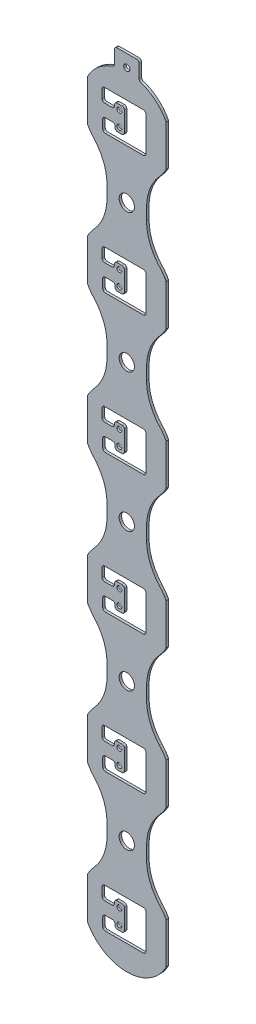
SolidWorks part; units mm, degrees
ref_plane "Plan de face" through (0, 0, 0) normal (0, 0, 1) x (1, 0, 0)
ref_plane "Plan de dessus" through (0, 0, 0) normal (0, 1, 0) x (1, 0, 0)
ref_plane "Plan de droite" through (0, 0, 0) normal (1, 0, 0) x (0, 0, -1)
sketch "Esquisse1" plane through (0, 0, 0) normal (0, 0, 1) x (1, 0, 0)
  line L1 (4, -28) -> (-4, -28)
  line L2 (4, -28) -> (4, -8.0623)
  line L4 (-4, -28) -> (-4, -8.0623)
  arc A0 (4, -8.0623) -> (-4, -8.0623) centre (0, 0) ccw
  point P4 (0, -28)
  dimension "D1" = 18
  dimension "D2" = 28
  dimension "D3" = 8
extrude "Boss.-Extru.1" add sketch "Esquisse1" along normal blind 0.508 contours A0 L4 L1 L2
pattern_linear "Répétition linéaire1" count 6 spacing 28 along (0, -1, 0) of "Boss.-Extru.1"
sketch "Esquisse2" plane through (0, 0, 0.508) normal (0, 0, 1) x (1, 0, 0)
  line L0 (-4, -168) -> (-4, -148.0623) construction
  line L1 (4, -168) -> (4, -148.0623) construction
  line L2 (4, -168) -> (-4, -168) construction
  line L12 (-4, -168) -> (-4, -148.0623)
  line L13 (4, -168) -> (4, -148.0623)
  line L14 (4, -168) -> (-4, -168)
  arc A2 (-4, -148.0623) -> (4, -148.0623) centre (0, -140) ccw
extrude "Enlèv. mat.-Extru.1" cut sketch "Esquisse2" against normal through all
sketch "Esquisse3" plane through (0, 0, 0.508) normal (0, 0, 1) x (1, 0, 0)
  line L0 (-3.875, 2.5) -> (-3.875, 4)
  line L1 (-3.875, -4) -> (3.875, -4)
  line L2 (-3.875, -4) -> (-3.875, -2.5)
  line L3 (-3.875, 4) -> (3.875, 4)
  line L4 (3.875, -4) -> (3.875, 4)
  line L5 (-3.875, -4) -> (3.875, 4) construction
  line L6 (-3.875, 4) -> (3.875, -4) construction
  line L7 (-3.875, 2.5) -> (-0.5, 2.5)
  line L9 (-3.875, -2.5) -> (-0.5, -2.5)
  line L10 (-0.5, 2.5) -> (-0.5, -2.5)
  point P0 (0, 0)
  point P10 (-0.5, 0)
  dimension "D1" = 8
  dimension "D2" = 7.75
  dimension "D3" = 0.5
  dimension "D4" = 5
extrude "Enlèv. mat.-Extru.2" cut sketch "Esquisse3" against normal through all
fillet "Congé1" radius 0.5 8 edges at (3.875, -4, 0.254) (3.875, 4, 0.254) (-3.875, -2.5, 0.254) (-3.875, -4, 0.254) (-0.5, -2.5, 0.254) (-0.5, 2.5, 0.254) (-3.875, 2.5, 0.254) (-3.875, 4, 0.254)
sketch "Esquisse4" plane through (0, 0, 0.508) normal (0, 0, 1) x (1, 0, 0)
  line L0 (-0.5, 2) -> (-0.5, -2) construction
  line L1 (-3.375, 2.5) -> (-1, 2.5) construction
  line L2 (-1, -2.5) -> (-3.375, -2.5) construction
  circle A0 centre (-1.5, 1.5) radius 0.5
  circle A1 centre (-1.5, -1.5) radius 0.5
  dimension "D1" = 1
  dimension "D2" = 1
  dimension "D3" = 1
  dimension "D4" = 1
extrude "Enlèv. mat.-Extru.3" cut sketch "Esquisse4" against normal blind 0.2
sketch "Esquisse5" plane through (0, 0, 0) normal (0, 0, -1) x (-1, 0, 0)
  circle A0 centre (1.5, -1.5) radius 0.5 construction
  circle A1 centre (1.5, 1.5) radius 0.5 construction
  circle A2 centre (1.5, -1.5) radius 0.5 construction
  circle A3 centre (1.5, 1.5) radius 0.5 construction
  circle A4 centre (1.5, 1.5) radius 0.6
  circle A5 centre (1.5, -1.5) radius 0.6
  dimension "D1" = 0.1
  dimension "D2" = 0.1
extrude "Boss.-Extru.2" add sketch "Esquisse5" along normal blind 0.2
fillet "Congé2" radius 0.2 4 edges at (-1, -1.5, 0.308) (-1, 1.5, 0.308) (-2.1, -1.5, -0.2) (-2.1, 1.5, -0.2)
pattern_linear "Répétition linéaire2" count 6 spacing 28 along (0, -1, 0) of "Congé2", "Boss.-Extru.2", "Enlèv. mat.-Extru.3", "Enlèv. mat.-Extru.2", "Enlèv. mat.-Extru.1", "Congé1"
fillet "Congé4" radius 10 20 edges at (4, -8.0623, 0.254) (-4, -19.9377, 0.254) (4, -19.9377, 0.254) (-4, -8.0623, 0.254) (-4, -47.9377, 0.254) (4, -47.9377, 0.254) (4, -64.0623, 0.254) (-4, -75.9377, 0.254) (4, -75.9377, 0.254) (4, -103.9377, 0.254) (-4, -103.9377, 0.254) (-4, -131.9377, 0.254) (4, -131.9377, 0.254) (4, -120.0623, 0.254) (-4, -120.0623, 0.254) (-4, -92.0623, 0.254) (4, -92.0623, 0.254) (-4, -64.0623, 0.254) (-4, -36.0623, 0.254) (4, -36.0623, 0.254)
sketch "Esquisse6" plane through (0, 0, 0.508) normal (0, 0, 1) x (1, 0, 0)
  line L1 (-8, 10.3107) -> (7.9883, 10.3107)
  line L2 (-8, 10.3107) -> (-8, -166.703)
  line L3 (-8, -166.703) -> (7.9883, -166.703)
  line L4 (7.9883, 10.3107) -> (7.9883, -166.703)
  arc A0 (6.6316, -6.0846) -> (-6.6316, -6.0846) centre (0, 0) ccw construction
  point P4 (8.9883, 0.4591)
  point P5 (-9, 0)
  dimension "D1" = 1
  dimension "D2" = 1
extrude "Enlèv. mat.-Extru.4" cut sketch "Esquisse6" against normal through all flip side to cut
sketch "Esquisse7" plane through (0, 0, 0.508) normal (0, 0, 1) x (1, 0, 0)
  line L0 (0, 0) -> (0, -28) construction
  line L2 (-0.5, -26) -> (-0.5, -30) construction
  line L3 (0, -28) -> (-0.5, -28) construction
  circle A0 centre (0, -14) radius 1.55
  circle A1 centre (0, -42) radius 1.55
  circle A2 centre (0, -70) radius 1.55
  circle A3 centre (0, -98) radius 1.55
  circle A4 centre (0, -126) radius 1.55
  point P9 (0, -14)
  dimension "D1" = 3.1
  dimension "D3" = 28
  dimension "D2" = 5
extrude "Enlèv. mat.-Extru.5" cut sketch "Esquisse7" against normal through all
sketch "Esquisse8" plane through (0, 0, 0.508) normal (0, 0, 1) x (1, 0, 0)
  line L1 (-2.5, 12.2) -> (2.5, 12.2)
  line L2 (-2.5, 12.2) -> (-2.5, 7.2)
  line L3 (-2.5, 7.2) -> (2.5, 7.2)
  line L4 (2.5, 12.2) -> (2.5, 7.2)
  line L5 (-2.5, 12.2) -> (2.5, 7.2) construction
  line L6 (-2.5, 7.2) -> (2.5, 12.2) construction
  circle A0 centre (0, 9.7) radius 0.625
  point P0 (0, 9.7)
  dimension "D4" = 1.25
  dimension "D1" = 5
  dimension "D2" = 7.2
  dimension "D3" = 5
extrude "Boss.-Extru.3" add sketch "Esquisse8" against normal up to surface (0.508 mm away) up to face at (1.55, -14, 0)
fillet "Congé5" radius 0.5 4 edges at (2.5, 8.6458, 0.254) (2.5, 12.2, 0.254) (-2.5, 12.2, 0.254) (-2.5, 8.6458, 0.254)
sketch "Esquisse9" plane through (0, 0, 0.508) normal (0, 0, 1) x (1, 0, 0)
  line L0 (-3.375, -4) -> (3.375, -4) construction
  line L1 (-5, 4) -> (-2.5, 4)
  line L2 (-5, 4) -> (-5, 1.25)
  line L3 (-5, 1.25) -> (-2.5, 1.25)
  line L4 (-2.5, 4) -> (-2.5, 1.25)
  line L5 (-4.875, -4) -> (-2.375, -4)
  line L6 (-4.875, -4) -> (-4.875, -1.25)
  line L7 (-4.875, -1.25) -> (-2.375, -1.25)
  line L8 (-2.375, -4) -> (-2.375, -1.25)
  line L9 (3.375, 4) -> (-3.375, 4) construction
  circle A0 centre (-1.5, 1.5) radius 0.5 construction
  dimension "D1" = 2.5
  dimension "D2" = 2.5
  dimension "D3" = 1
extrude "Enlèv. mat.-Extru.6" cut sketch "Esquisse9" against normal through all
pattern_linear "Répétition linéaire3" count 6 spacing 28 along (0, -1, 0) of "Enlèv. mat.-Extru.6"
fillet "Congé6" radius 0.5 8 edges at (-4.875, -4, 0.254) (-2.375, -1.25, 0.254) (-4.875, -1.25, 0.254) (-2.375, -2.5, 0.254) (-2.5, 1.25, 0.254) (-2.5, 2.5, 0.254) (-5, 1.25, 0.254) (-5, 4, 0.254)
fillet "Congé7" radius 0.5 40 edges at (-5, -24, 0.254) (-2.5, -26.75, 0.254) (-4.875, -32, 0.254) (-2.375, -30.5, 0.254) (-2.375, -29.25, 0.254) (-4.875, -29.25, 0.254) (-5, -26.75, 0.254) (-2.5, -25.5, 0.254) (-2.375, -141.25, 0.254) (-4.875, -141.25, 0.254) (-5, -136, 0.254) (-5, -138.75, 0.254) (-4.875, -144, 0.254) (-2.5, -137.5, 0.254) (-2.5, -138.75, 0.254) (-2.375, -142.5, 0.254) (-2.5, -110.75, 0.254) (-2.375, -113.25, 0.254) (-2.375, -114.5, 0.254) (-4.875, -113.25, 0.254) (-5, -108, 0.254) (-2.5, -109.5, 0.254) (-4.875, -116, 0.254) (-5, -110.75, 0.254) (-4.875, -88, 0.254) (-5, -82.75, 0.254) (-5, -80, 0.254) (-4.875, -85.25, 0.254) (-2.375, -85.25, 0.254) (-2.375, -86.5, 0.254) (-2.5, -82.75, 0.254) (-2.5, -81.5, 0.254) (-2.375, -57.25, 0.254) (-4.875, -57.25, 0.254) (-5, -52, 0.254) (-5, -54.75, 0.254) (-4.875, -60, 0.254) (-2.375, -58.5, 0.254) (-2.5, -54.75, 0.254) (-2.5, -53.5, 0.254)
